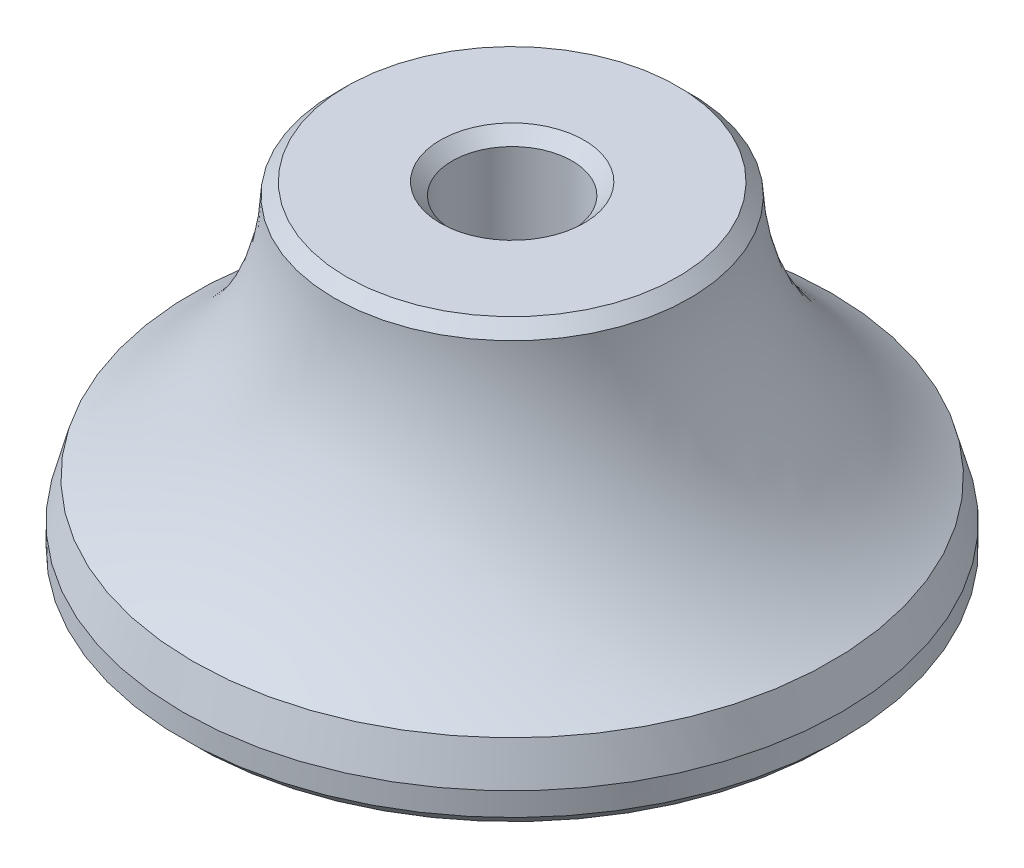
SolidWorks part; units mm, degrees
ref_plane "Front Plane" through (0, 0, 0) normal (0, 0, 1) x (1, 0, 0)
ref_plane "Top Plane" through (0, 0, 0) normal (0, 1, 0) x (1, 0, 0)
ref_plane "Right Plane" through (0, 0, 0) normal (1, 0, 0) x (0, 0, -1)
sketch "Sketch1" plane through (0, 0, 0) normal (0, 0, 1) x (1, 0, 0)
  line L0 (0, 0) -> (0, 50000) construction
  line L1 (25.4, 0) -> (25.4, 50000) construction
  line L2 (17.4625, 0) -> (17.4625, -13.8946) construction
  line L3 (17.4625, -17.4625) -> (17.4625, -13.8946)
  line L4 (0, 0) -> (0, -17.4625)
  line L5 (0, -17.4625) -> (17.4625, -17.4625)
  line L6 (9.398, 0) -> (0, 0)
  line L8 (17.4625, 0) -> (17.4625, 50000) construction
  arc A0 (9.398, 0) -> (17.4625, -13.8946) centre (25.4, 0) ccw
  dimension "D2" = 32.004
  dimension "D4" = 17.4625
  dimension "D1" = 25.4
  dimension "D3" = 7.9375
revolve "Revolve1" add sketch "Sketch1" angle 360 about L0
sketch "Sketch2" plane through (0, 0, 0) normal (0, 1, 0) x (1, 0, 0)
  circle A0 centre (0, 0) radius 3.175
  dimension "D1" = 6.35
extrude "Cut-Extrude1" cut sketch "Sketch2" against normal through all both and the other way through all
chamfer "Chamfer1" distance 0.635 angle 45 5 edges at (0, -17.4625, -17.4625) (0, -17.4625, 3.175) (0, -13.8946, -17.4625) (0, 0, -9.398) (0, 0, 3.175) first distance on face at (0, -13.8946, -17.4625) first distance on face at (0, 0, 3.175) first distance on face at (0, 0, -9.398)
